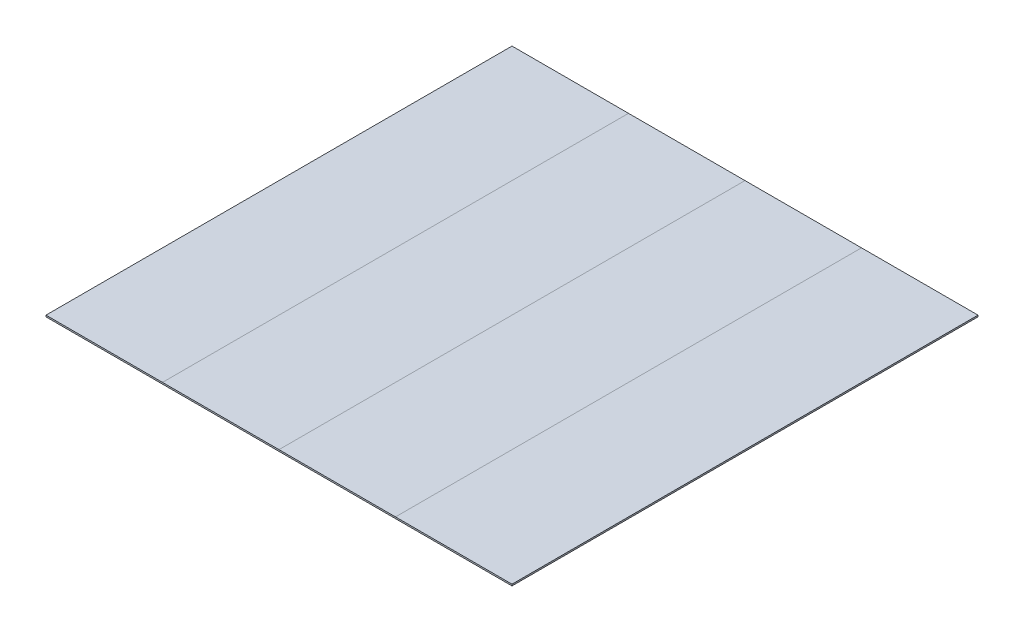
SolidWorks part; units mm, degrees
ref_plane "Front Plane" through (0, 0, 0) normal (0, 0, 1) x (1, 0, 0)
ref_plane "Top Plane" through (0, 0, 0) normal (0, 1, 0) x (1, 0, 0)
ref_plane "Right Plane" through (0, 0, 0) normal (1, 0, 0) x (0, 0, -1)
sketch "Sketch8" plane through (0, 0, 0) normal (0, 1, 0) x (1, 0, 0)
  line L1 (-296.5616, -440.5444) -> (1203.4384, -440.5444)
  line L2 (-296.5616, -440.5444) -> (-296.5616, 1059.4556)
  line L3 (-296.5616, 1059.4556) -> (1203.4384, 1059.4556)
  line L4 (1203.4384, -440.5444) -> (1203.4384, 1059.4556)
  line L5 (78.4384, 1059.4556) -> (828.4384, 1059.4556)
  line L6 (78.4384, 1059.4556) -> (78.4384, -440.5444)
  line L7 (78.4384, -440.5444) -> (828.4384, -440.5444)
  line L8 (828.4384, 1059.4556) -> (828.4384, -440.5444)
  dimension "D1" = 1500
  dimension "D2" = 1500
  dimension "D3" = 750
  dimension "D4" = 1500
extrude "Boss-Extrude18" add sketch "Sketch8" along normal blind 5 contours L8 L3 L6 L1 | L3 L8 L1 L4 | L6 L3 L2 L1 region at (-109.0616, 0, -309.4556) region at (453.4384, 0, -309.4556) region at (1015.9384, 0, -309.4556)
split line "Split Line26"
sketch "Sketch8<3>" plane through (0, 0, 0) normal (0, 1, 0) x (1, 0, 0) same geometry as "Sketch8"
sketch "Sketch9" plane through (0, 5, 0) normal (0, 1, 0) x (1, 0, 0)
  line L0 (78.4384, -440.5444) -> (828.4384, -440.5444) construction
  line L1 (78.4384, 1059.4556) -> (453.4384, 1059.4556)
  line L2 (78.4384, 1059.4556) -> (78.4384, -440.5444)
  line L3 (78.4384, -440.5444) -> (453.4384, -440.5444)
  line L4 (453.4384, 1059.4556) -> (453.4384, -440.5444)
split line "Split Line27"
equation "\"Scale\"= 8"
equation "\"Tile Size\"= \"Road Size\" * 2"
equation "\"Road Size\"= \"Real Lane Size\" * 2 / \"Scale\""
equation "\"Real Lane Size\"= 3m"
